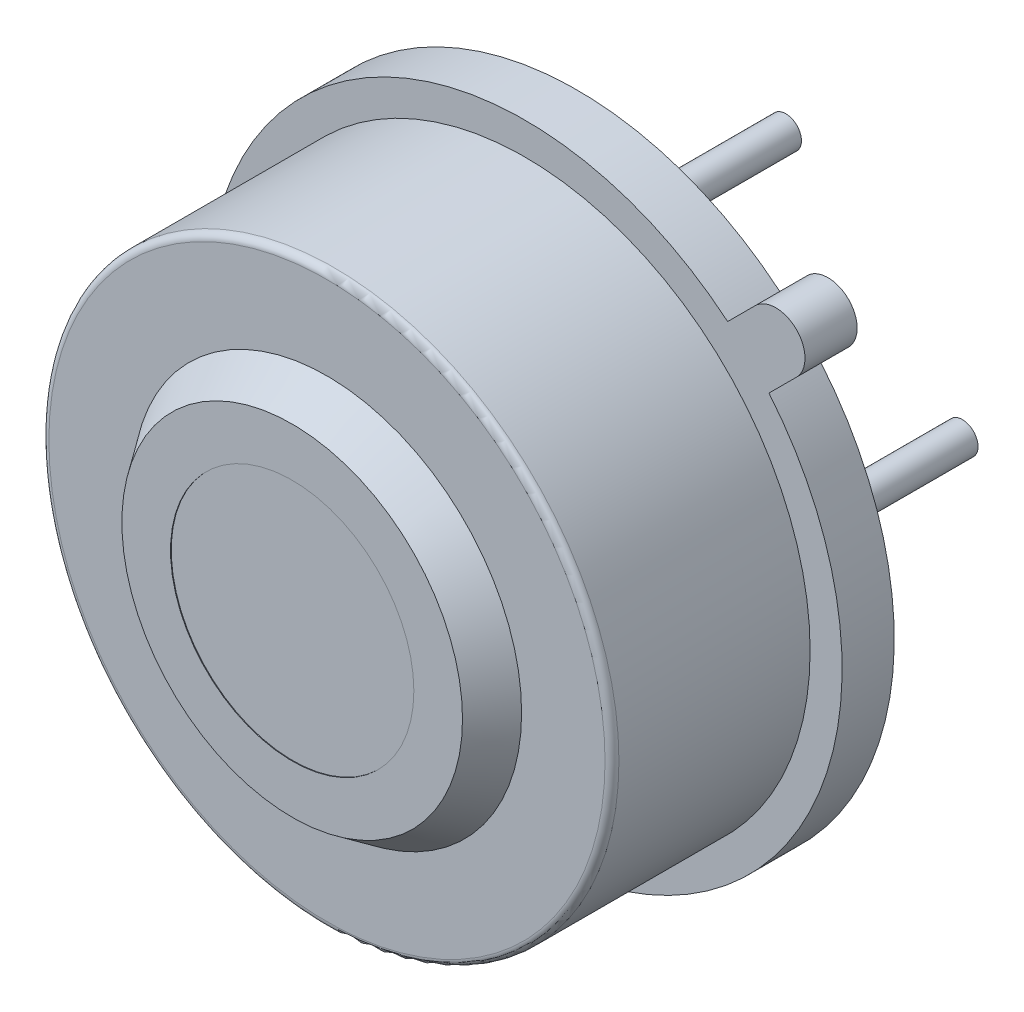
SolidWorks part; units mm, degrees
other "Детальный элемент1"
ref_plane "Спереди" through (0, 0, 0) normal (0, 0, 1) x (1, 0, 0)
ref_plane "Сверху" through (0, 0, 0) normal (0, 1, 0) x (1, 0, 0)
ref_plane "Справа" through (0, 0, 0) normal (1, 0, 0) x (0, 0, -1)
sketch "Эскиз1" plane through (0, 0, 0) normal (0, 0, 1) x (1, 0, 0)
  line L0 (2.9137, 3.5077) -> (3.3093, 3.9032)
  line L1 (3.5077, 2.9137) -> (3.9032, 3.3093)
  line L2 (50, 0) -> (-50, 0) construction
  arc A1 (3.5077, 2.9137) -> (2.9137, 3.5077) centre (0, 0) cw
  arc A2 (3.3093, 3.9032) -> (3.9032, 3.3093) centre (3.6062, 3.6062) cw
  point P10 (3.9032, 3.9032)
  dimension "D1" = 4.56
  dimension "D2" = 45
  dimension "D3" = 5.52
  dimension "D4" = 0.42
  dimension "D5" = 0.42
extrude "Бобышка-Вытянуть1" add sketch "Эскиз1" along normal blind 0.75
sketch "Эскиз2" plane through (0, 0, 0.75) normal (0, 0, 1) x (1, 0, 0)
  circle A0 centre (0, 0) radius 4.1
  dimension "D1" = 8.2
extrude "Бобышка-Вытянуть2" add sketch "Эскиз2" along normal blind 2.85
sketch "Эскиз3" plane through (0, 0, 3.6) normal (0, 0, 1) x (1, 0, 0)
  circle A0 centre (0, 0) radius 2.8
  dimension "D1" = 5.6
extrude "Бобышка-Вытянуть3" add sketch "Эскиз3" along normal blind 0.5
sketch "Эскиз4" plane through (0, 0, 4.1) normal (0, 0, 1) x (1, 0, 0)
  circle A0 centre (0, 0) radius 1.75
  dimension "D1" = 3.5
extrude "Вырез-Вытянуть1" cut sketch "Эскиз4" against normal blind 0.01
fillet "Скругление1" radius 0.1 1 edges at (4.1, 0, 3.6)
chamfer "Фаска1" distance 0.5 angle 35 1 edges at (2.8, 0, 4.1) first distance on face at (2.8, 0, 4.1)
sketch "Эскиз5" plane through (0, 0, 0) normal (0, 0, -1) x (-1, 0, 0)
  circle A0 centre (-2.54, 0) radius 0.225
  circle A1 centre (0, -2.54) radius 0.225
  circle A2 centre (2.54, 0) radius 0.225
  circle A3 centre (0, 2.54) radius 0.225
  point P8 (0, 0)
  point P9 (0, 0)
  point P10 (2.8584, 0)
  point P11 (0, 0)
  point P13 (0, 0)
  point P14 (0, 0)
  dimension "D5" = 0.45
  dimension "D1" = 2.54
  dimension "D2" = 2.54
  dimension "D3" = 2.54
  dimension "D4" = 2.54
extrude "Бобышка-Вытянуть4" add sketch "Эскиз5" along normal blind 3
